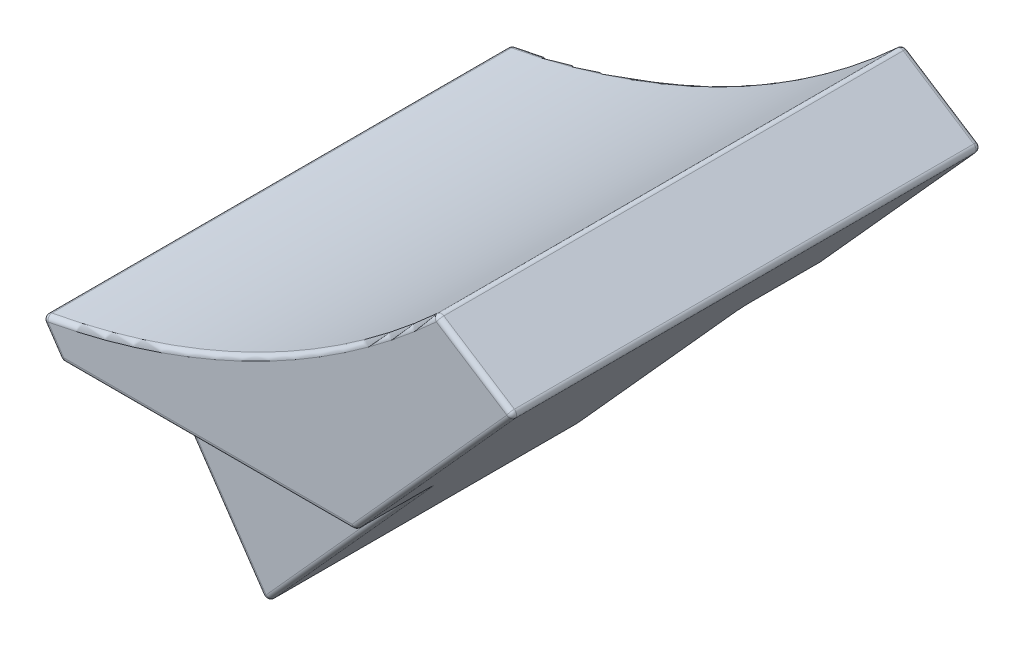
SolidWorks part; units mm, degrees
material "NEOPRENE"
ref_plane "Front Plane" through (0, 0, 0) normal (0, 0, 1) x (1, 0, 0)
ref_plane "Top Plane" through (0, 0, 0) normal (0, 1, 0) x (1, 0, 0)
ref_plane "Right Plane" through (0, 0, 0) normal (1, 0, 0) x (0, 0, -1)
sketch "Profile Sketch" plane through (0, 0, 0) normal (0, 0, 1) x (1, 0, 0)
  line L7 (0, 79.275) -> (0, -79.275) construction
  line L8 (27.2106, -29.3187) -> (31.2283, -31.9106)
  line L9 (31.2283, -31.9106) -> (14.5, -50.4892)
  line L10 (14.5, -50.4892) -> (6.9499, -39.3916)
  arc A8 (6.9499, -39.3916) -> (27.2106, -29.3187) centre (0, 0) ccw
  point P15 (0, 0)
  point P55 (14.5, -50.4892)
  point P58 (31.2283, -31.9106)
  dimension "D1" = 6.9499
  dimension "D9" = 40
  dimension "D3" = 4.7812
  dimension "D4" = 13.4224
  dimension "D6" = 25
  dimension "D7" = 14.5
  dimension "D8" = 42
extrude "Body" add sketch "Profile Sketch" along normal mid plane 24
sketch "Front Cut Out Sketch" plane through (0, 0, 0) normal (0, 0, 1) x (1, 0, 0)
  line L0 (6.9499, -39.3916) -> (14.5, -50.4892) construction
  line L1 (8.0442, -41) -> (23.0441, -41)
  line L2 (8.0442, -41) -> (8.0442, -50.4892)
  line L3 (8.0442, -50.4892) -> (23.0441, -50.4892)
  line L4 (23.0441, -41) -> (23.0441, -50.4892)
  line L5 (8.0442, -41) -> (23.0441, -50.4892) construction
  line L6 (8.0442, -50.4892) -> (23.0441, -41) construction
  line L7 (14.5, -50.4892) -> (31.2283, -31.9106) construction
  point P0 (15.5441, -45.7446)
  dimension "D1" = 41
extrude "Front Cut Out" cut sketch "Front Cut Out Sketch" along normal through all from offset 8
mirror "Back Cut" about plane through (0, 0, 0) normal (0, 0, 1) of "Front Cut Out"
fillet "Fillet Edges" radius 0.25 24 edges at (15.5441, -41, 8) (15.5441, -41, -8) (15.5441, -41, -12) (15.5441, -41, 12) (18.7721, -45.7446, 8) (23.0441, -41, 10) (27.1362, -36.4553, 12) (27.1362, -36.4553, -12) (23.0441, -41, -10) (18.7721, -45.7446, -8) (31.2283, -31.9106, 0) (29.2194, -30.6146, 12) (29.2194, -30.6146, -12) (27.2106, -29.3187, 0) (17.8073, -35.8176, 12) (17.8073, -35.8176, -12) (6.9499, -39.3916, 0) (7.497, -40.1958, 12) (8.0442, -41, 10) (11.2721, -45.7446, 8) (14.5, -50.4892, 0) (11.2721, -45.7446, -8) (8.0442, -41, -10) (7.497, -40.1958, -12)
